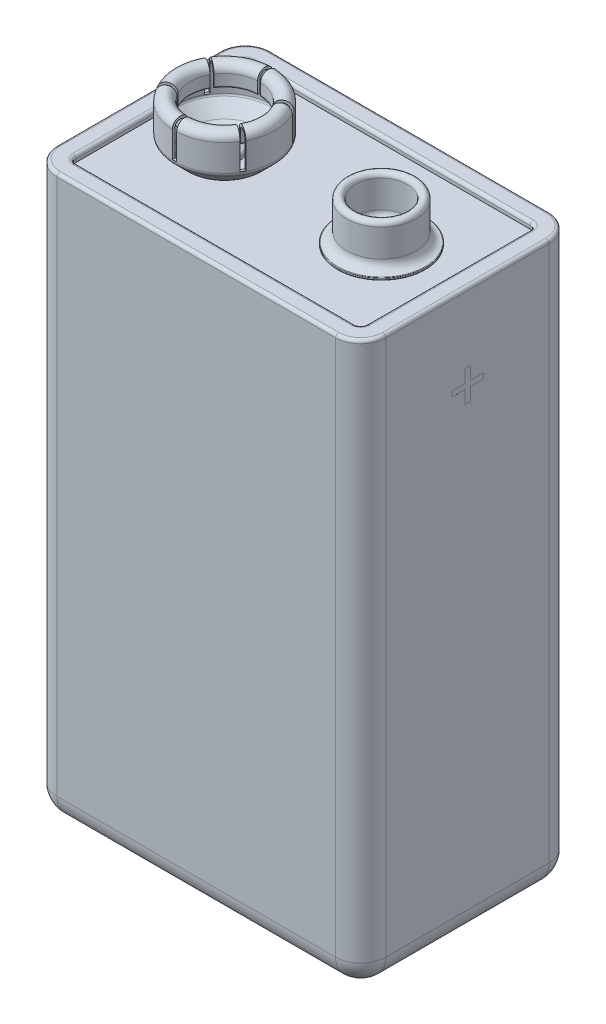
SolidWorks part; units mm, degrees
note: The reader was unsure of these and kept them because the rebuilt part matched: shared geometry of "Anschluss Pluspol_Skizze<3>".
material "1060 Legierung"
ref_plane "Ebene vorne" through (0, 0, 0) normal (0, 0, 1) x (1, 0, 0)
ref_plane "Ebene oben" through (0, 0, 0) normal (0, 1, 0) x (1, 0, 0)
ref_plane "Ebene rechts" through (0, 0, 0) normal (1, 0, 0) x (0, 0, -1)
sketch "Grundkörper_Skizze" plane through (0, 0, 0) normal (0, 1, 0) x (1, 0, 0)
  line L1 (13.1, -8.5) -> (-13.1, -8.5)
  line L2 (13.1, -8.5) -> (13.1, 8.5)
  line L3 (13.1, 8.5) -> (-13.1, 8.5)
  line L4 (-13.1, -8.5) -> (-13.1, 8.5)
  line L5 (13.1, -8.5) -> (-13.1, 8.5) construction
  line L6 (13.1, 8.5) -> (-13.1, -8.5) construction
  point P0 (0, 0)
  dimension "D1" = 17
  dimension "D2" = 26.2
extrude "Grundkörper_Aufsatz austragen" add sketch "Grundkörper_Skizze" along normal mid plane 45
fillet "Grundkörper_Verrundung" radius 2 8 edges at (0, -22.5, 8.5) (13.1, -22.5, 0) (0, -22.5, -8.5) (-13.1, -22.5, 0) (13.1, 0, -8.5) (-13.1, 0, -8.5) (13.1, 0, 8.5) (-13.1, 0, 8.5)
sketch "Vertiefung Anschlüsse_Skizze" plane through (0, 22.5, 0) normal (0, 1, 0) x (1, 0, 0)
  line L8 (11.6, -6.5) -> (11.6, 6.5)
  line L9 (11.1, 7) -> (-11.1, 7)
  line L10 (-11.6, 6.5) -> (-11.6, -6.5)
  line L11 (-11.1, -7) -> (11.1, -7)
  line L12 (11.6, -6.5) -> (11.6, 6.5)
  line L13 (11.1, 7) -> (-11.1, 7)
  line L14 (-11.6, 6.5) -> (-11.6, -6.5)
  line L15 (-11.1, -7) -> (11.1, -7)
  arc A8 (11.6, 6.5) -> (11.1, 7) centre (11.1, 6.5) ccw
  arc A9 (-11.1, 7) -> (-11.6, 6.5) centre (-11.1, 6.5) ccw
  arc A10 (-11.6, -6.5) -> (-11.1, -7) centre (-11.1, -6.5) ccw
  arc A11 (11.1, -7) -> (11.6, -6.5) centre (11.1, -6.5) ccw
  arc A12 (11.6, 6.5) -> (11.1, 7) centre (11.1, 6.5) ccw
  arc A13 (-11.1, 7) -> (-11.6, 6.5) centre (-11.1, 6.5) ccw
  arc A14 (-11.6, -6.5) -> (-11.1, -7) centre (-11.1, -6.5) ccw
  arc A15 (11.1, -7) -> (11.6, -6.5) centre (11.1, -6.5) ccw
  dimension "D1" = 1.5
extrude "Vertiefung Anschlüsse_Schnitt austragen" cut sketch "Vertiefung Anschlüsse_Skizze" against normal blind 0.5
fillet "Vertiefung Anschlüsse_Verrundung" radius 0.25 16 edges at (12.5142, 22.5, 7.9142) (0, 22.5, 8.5) (-12.5142, 22.5, 7.9142) (-13.1, 22.5, 0) (-12.5142, 22.5, -7.9142) (0, 22.5, -8.5) (12.5142, 22.5, -7.9142) (13.1, 22.5, 0) (11.6, 22.5, 0) (11.4536, 22.5, -6.8536) (0, 22.5, -7) (-11.4536, 22.5, -6.8536) (-11.6, 22.5, 0) (-11.4536, 22.5, 6.8536) (0, 22.5, 7) (11.4536, 22.5, 6.8536)
sketch "Anschlüsse_Skizze" plane through (0, 0, 0) normal (0, 0, 1) x (1, 0, 0)
  line L0 (9.75, 22.05) -> (9.75, 22.1516)
  line L1 (-11.1, 22) -> (11.1, 22) construction
  line L2 (9.7, 22) -> (6.25, 22)
  line L3 (7.5, 22.45) -> (7.8, 22.45)
  line L4 (8.3, 22.95) -> (8.3, 25.15)
  line L5 (-6.25, 0) -> (6.25, 0) construction
  line L6 (9, 22.95) -> (9, 25.15)
  line L7 (6.25, 22) -> (6.25, 22.3)
  line L8 (6.65, 22.7) -> (7.25, 22.7)
  line L9 (-7.5, 22.2) -> (-8.5, 22.2)
  line L10 (-6.25, 22) -> (-8.5, 22)
  line L12 (-9.2071, 22.2929) -> (-10.1339, 23.2197)
  line L15 (-9.9925, 23.3611) -> (-9.0657, 22.4343)
  line L18 (-10.25, 23.55) -> (-10.05, 23.55)
  line L19 (-10.05, 23.55) -> (-10.05, 23.5)
  line L20 (-10.25, 23.55) -> (-10.25, 23.5)
  line L21 (-6.65, 22.7) -> (-7.25, 22.7)
  line L22 (-6.25, 22) -> (-6.25, 22.3)
  line L23 (-7.5, 22.45) -> (-7.5, 22.2)
  line L24 (-10.25, 23.5) -> (-10.2592, 23.5071)
  arc A0 (9, 25.15) -> (8.3, 25.15) centre (8.65, 25.15) ccw
  arc A1 (9.7031, 22.2015) -> (9, 22.95) centre (9.75, 22.95) cw
  arc A2 (7.8, 22.45) -> (8.3, 22.95) centre (7.8, 22.95) ccw
  arc A3 (9.75, 22.05) -> (9.7, 22) centre (9.7, 22.05) cw
  arc A4 (9.75, 22.1516) -> (9.7031, 22.2015) centre (9.7, 22.1516) ccw
  arc A5 (6.25, 22.3) -> (6.4, 22.45) centre (6.25, 22.45) ccw
  arc A6 (6.4, 22.45) -> (6.65, 22.7) centre (6.65, 22.45) cw
  arc A7 (7.25, 22.7) -> (7.5, 22.45) centre (7.25, 22.45) cw
  arc A8 (-8.5, 22) -> (-9.2071, 22.2929) centre (-8.5, 23) cw
  arc A9 (-10.1339, 23.2197) -> (-10.25, 23.5) centre (-9.8536, 23.5) cw
  arc A12 (-9.9925, 23.3611) -> (-10.05, 23.5) centre (-9.8536, 23.5) cw
  arc A13 (-9.0657, 22.4343) -> (-8.5, 22.2) centre (-8.5, 23) ccw
  arc A14 (-7.25, 22.7) -> (-7.5, 22.45) centre (-7.25, 22.45) ccw
  arc A15 (-6.4, 22.45) -> (-6.65, 22.7) centre (-6.65, 22.45) ccw
  arc A16 (-6.25, 22.3) -> (-6.4, 22.45) centre (-6.25, 22.45) cw
  point P14 (8.65, 25.5)
  point P20 (9.75, 22)
  point P23 (9.75, 22.2)
  dimension "D1" = 3.5
  dimension "D3" = 3.5
  dimension "D4" = 0.7
  dimension "D6" = 0.5
  dimension "D7" = 0.05
  dimension "D9" = 1.25
  dimension "D12" = 0.15
  dimension "D10" = 0.25
  dimension "D13" = 0.15
  dimension "D15" = 0.25
  dimension "D21" = 1
  dimension "D2" = 12.5
  dimension "D5" = 0.2
  dimension "D8" = 2.75
  dimension "D11" = 0.3
  dimension "D14" = 1.25
  dimension "D16" = 0.2
  dimension "D17" = 0.3
  dimension "D18" = 4
  dimension "D24" = 135
  dimension "D25" = 1
  dimension "D26" = 1.5
  dimension "D27" = 0.05
revolve "Anschluss Pluspol_Rotation" add sketch "Anschlüsse_Skizze" angle 360 about L7
revolve "Anschluss Minuspol Basis_Rotation" add sketch "Anschluss Pluspol_Skizze<3>" angle 360 about L22
sketch "Anschluss Pluspol_Skizze<3>" plane through (0, 0, 0) normal (0, 0, 1) x (1, 0, 0) same geometry as "Anschlüsse_Skizze"
sketch "Anschluss Minuspol_Skizze" plane through (0, 0, 0) normal (0, 0, 1) x (1, 0, 0)
  line L0 (-10.25, 23.55) -> (-10.05, 23.55)
  line L1 (-10.25, 23.55) -> (-10.25, 25.625)
  line L2 (-9, 25.625) -> (-9, 24.75)
  line L3 (-9.2, 24.75) -> (-9.2, 25.625)
  line L4 (-10.05, 25.625) -> (-10.05, 23.55)
  line L5 (11.1, 22.25) -> (-11.1, 22.25) construction
  arc A0 (-10.25, 25.625) -> (-9, 25.625) centre (-9.625, 25.625) cw
  arc A1 (-9.2, 25.625) -> (-10.05, 25.625) centre (-9.625, 25.625) ccw
  arc A2 (-9, 24.75) -> (-9.2, 24.75) centre (-9.1, 24.75) cw
  point P10 (-9.625, 26.25)
  dimension "D1" = 1.25
  dimension "D2" = 0.2
  dimension "D3" = 1.5
  dimension "D4" = 4
revolve "Anschluss Minuspol_Rotation" add sketch "Anschluss Minuspol_Skizze" angle 55 mid plane
pattern_circular "Anschluss Minuspol_Kreismuster" count 6 over 360 about axis through (-6.25, 0, 0) along (0, 1, 0) of "Anschluss Minuspol_Rotation"
sketch "Beschriftung Pluspol_Skizze" plane through (13.1, 0, 0) normal (1, 0, 0) x (0, 0, -1)
  line L0 (-6.5, 17.5) -> (6.5, 17.5) construction
  line L1 (-6.5, 22.25) -> (-6.5, -20.5) construction
  line L2 (6.5, -20.5) -> (6.5, 22.25) construction
  line L3 (-6.5, 22.5) -> (6.5, 22.5) construction
  text T0 "<b>+</b>"
  dimension "D1" = 5
extrude "Beschriftung Pluspol_Schnitt austragen" cut sketch "Beschriftung Pluspol_Skizze" against normal blind 0.001
sketch "Beschriftung Minuspol_Skizze" plane through (-13.1, 0, 0) normal (-1, 0, 0) x (0, 0, 1)
  line L0 (-6.5, 17.5) -> (6.5, 17.5) construction
  line L1 (-6.5, 22.25) -> (-6.5, -20.5) construction
  line L2 (6.5, -20.5) -> (6.5, 22.25) construction
  line L3 (-6.5, 22.5) -> (6.5, 22.5) construction
  text T0 "−"
  dimension "D1" = 5
extrude "Beschriftung Minuspol_Schnitt austragen" cut sketch "Beschriftung Minuspol_Skizze" against normal blind 0.001
sketch "Sketch1" plane through (0, 0, 8.5) normal (0, 0, 1) x (1, 0, 0)
  line L0 (5.5285, 2.1206) -> (5.5285, -9.0267) construction
